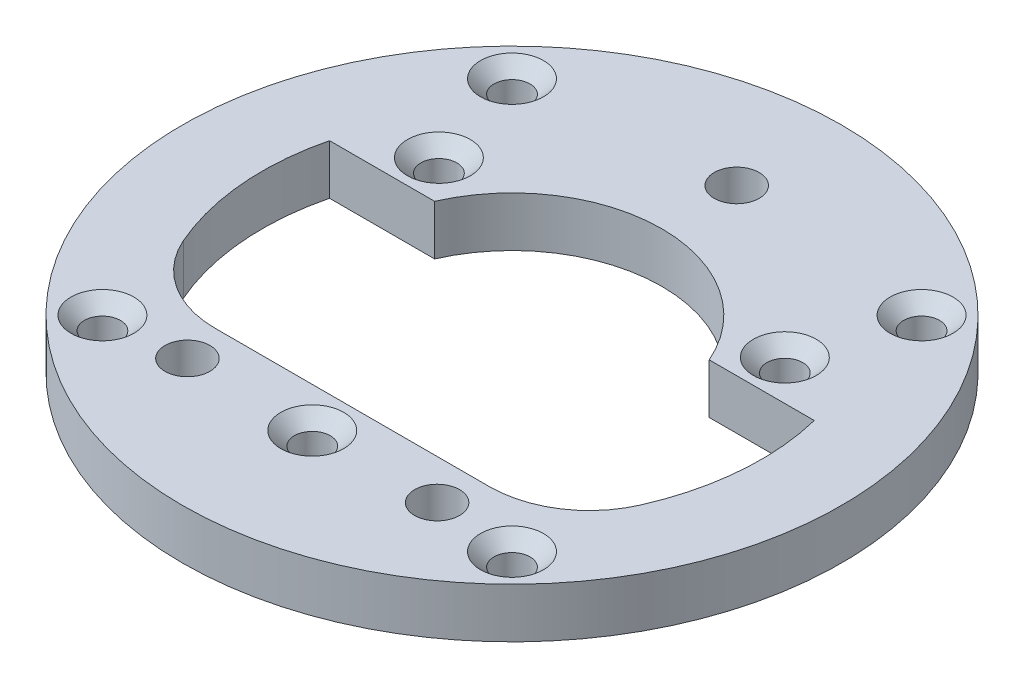
SolidWorks part; units mm, degrees
ref_plane "Front Plane" through (0, 0, 0) normal (0, 0, 1) x (1, 0, 0)
ref_plane "Top Plane" through (0, 0, 0) normal (0, 1, 0) x (1, 0, 0)
ref_plane "Right Plane" through (0, 0, 0) normal (1, 0, 0) x (0, 0, -1)
sketch "Sketch1" plane through (0, 0, 0) normal (0, 1, 0) x (1, 0, 0)
  circle A0 centre (0, 0) radius 33
  circle A1 centre (0, 0) radius 25
  dimension "D1" = 66
  dimension "D2" = 8
extrude "Boss-Extrude1" add sketch "Sketch1" along normal blind 5
sketch "Sketch2" plane through (0, 5, 0) normal (0, 1, 0) x (1, 0, 0)
  line L0 (-19.2094, -16) -> (19.2094, -16)
  line L1 (-24.2693, 6) -> (-13.7477, 6)
  line L2 (0, 0) -> (7.7557, 0) construction
  line L3 (13.7477, 6) -> (24.2693, 6)
  line L4 (-20.5061, 20.5061) -> (0, 0) construction
  circle A0 centre (0, 22.5) radius 2.25 construction
  circle A1 centre (-12.5, -20) radius 2.25 construction
  circle A2 centre (12.5, -20) radius 2.25 construction
  circle A3 centre (0, -20) radius 1.5 construction
  circle A4 centre (0, 0) radius 20 construction
  circle A5 centre (-17.3205, 10) radius 1.5 construction
  circle A6 centre (0, 0) radius 25 construction
  circle A7 centre (17.3205, 10) radius 1.5 construction
  arc A8 (-13.7477, 6) -> (13.7477, 6) centre (0, 0) cw
  arc A9 (24.2693, 6) -> (-24.2882, 5.9232) centre (0, 0) ccw
  arc A10 (19.2094, -16) -> (-19.2094, -16) centre (0, 0) cw
  circle A12 centre (0, 0) radius 29 construction
  circle A13 centre (0, 0) radius 33 construction
  circle A14 centre (-20.5061, 20.5061) radius 1.75 construction
  circle A15 centre (20.5061, 20.5061) radius 1.75 construction
  circle A16 centre (20.5061, -20.5061) radius 1.75 construction
  circle A17 centre (-20.5061, -20.5061) radius 1.75 construction
  point P19 (0, 0)
  point P25 (0, 0)
  point P26 (0, 0)
  point P27 (0, 0)
  point P28 (0, 0)
  point P29 (0, 0)
  point P35 (0, 0)
  point P36 (-17.3205, 10.253)
  point P44 (0, 0)
  circle M2 centre (0, 0) radius 25
  dimension "D5" = 4.5
  dimension "D6" = 4.5
  dimension "D7" = 4.5
  dimension "D10" = 3
  dimension "D12" = 15
  dimension "D16" = 3.5
  dimension "D1" = 25
  dimension "D2" = 12.5
  dimension "D3" = 22.5
  dimension "D4" = 20
  dimension "D9" = 5
  dimension "D11" = 4
  dimension "D13" = 4
  dimension "D14" = 4
  dimension "D15" = 135
  dimension "D18" = 5
  dimension "D8" = 3
  dimension "D17" = 4
extrude "Saliente-Extruir1" add sketch "Sketch2" against normal up to surface (5 mm away) contours L1 A8 L3 M2 | L0 M2 region at (0, 5, 19.6621) region at (0, 5, -15.401) up to face at (0, 0, 33)
sketch "Croquis1" plane through (0, 5, 0) normal (0, 1, 0) x (1, 0, 0)
  circle A0 centre (-20.5061, 20.5061) radius 1.75 construction
  circle A1 centre (-20.5061, 20.5061) radius 1.75
  circle A2 centre (0, 22.5) radius 2.25 construction
  circle A3 centre (0, 22.5) radius 2.25
  circle A4 centre (20.5061, 20.5061) radius 1.75 construction
  circle A5 centre (20.5061, 20.5061) radius 1.75
  circle A6 centre (-17.3205, 10) radius 1.5 construction
  circle A7 centre (-17.3205, 10) radius 1.5
  circle A8 centre (17.3205, 10) radius 1.5 construction
  circle A9 centre (17.3205, 10) radius 1.5
  circle A10 centre (0, -20) radius 1.5 construction
  circle A11 centre (0, -20) radius 1.5
  circle A12 centre (12.5, -20) radius 2.25 construction
  circle A13 centre (12.5, -20) radius 2.25
  circle A14 centre (-12.5, -20) radius 2.25 construction
  circle A15 centre (-12.5, -20) radius 2.25
  circle A16 centre (-20.5061, -20.5061) radius 1.75 construction
  circle A17 centre (-20.5061, -20.5061) radius 1.75
  circle A18 centre (20.5061, -20.5061) radius 1.75 construction
  circle A19 centre (20.5061, -20.5061) radius 1.75
extrude "Cortar-Extruir1" cut sketch "Croquis1" against normal up to next
fillet "Redondeo1" radius 10 2 edges at (19.2094, 2.5, 16) (-19.2094, 2.5, 16)
hole_wizard "CSK for M3 Flat Head Machine Screw1" positions "Sketch4" profile "Sketch5" countersink size "M3" standard "ANSI Metric" end condition through all
sketch "Sketch4" plane through (0, 5, 0) normal (0, 1, 0) x (1, 0, 0)
  point P0 (-20.5061, 20.5061)
  point P3 (20.5061, 20.5061)
  point P6 (20.5061, -20.5061)
  point P9 (-20.5061, -20.5061)
sketch "Sketch5" plane through (-20.5061, 5, -20.5061) normal (1, 0, 0) x (0, 0, 1)
  line L0 (0, 0) -> (0, 5)
  line L1 (0, 5) -> (1.8, 5)
  line L2 (1.8, 5) -> (1.8, 1.35)
  line L3 (1.8, 1.35) -> (3.15, 0)
  line L5 (3.15, 0) -> (0, 0)
  line L6 (-1.8, 1.35) -> (-3.15, 0) construction
  line L11 (0, -6.35) -> (0, 107.95) construction
  dimension "Thru Hole Dia." = 3.6
  dimension "Thru Hole Depth" = 5
  dimension "Near C'Sink Dia." = 6.3
  dimension "Near C'Sink Angle" = 90
hole_wizard "CSK for M3 Flat Head Machine Screw2" positions "Sketch6" profile "Sketch7" countersink size "M3" standard "ANSI Metric" end condition through all
sketch "Sketch6" plane through (0, 5, 0) normal (0, 1, 0) x (1, 0, 0)
  point P0 (-17.3205, 10)
  point P3 (17.3205, 10)
  point P6 (0, -20)
sketch "Sketch7" plane through (-17.3205, 5, -10) normal (1, 0, 0) x (0, 0, 1)
  line L0 (0, 0) -> (0, 5)
  line L1 (0, 5) -> (1.8, 5)
  line L2 (1.8, 5) -> (1.8, 1.35)
  line L3 (1.8, 1.35) -> (3.15, 0)
  line L5 (3.15, 0) -> (0, 0)
  line L6 (-1.8, 1.35) -> (-3.15, 0) construction
  line L11 (0, -6.35) -> (0, 107.95) construction
  dimension "Thru Hole Dia." = 3.6
  dimension "Thru Hole Depth" = 5
  dimension "Near C'Sink Dia." = 6.3
  dimension "Near C'Sink Angle" = 90
equation "\"D2@Sketch2\"=\"D1@Sketch2\"/2"
equation "\"D6@Sketch2\"=\"D5@Sketch2\""
equation "\"D7@Sketch2\"=\"D6@Sketch2\""
equation "\"D10@Sketch2\"=\"D8@Sketch2\""
